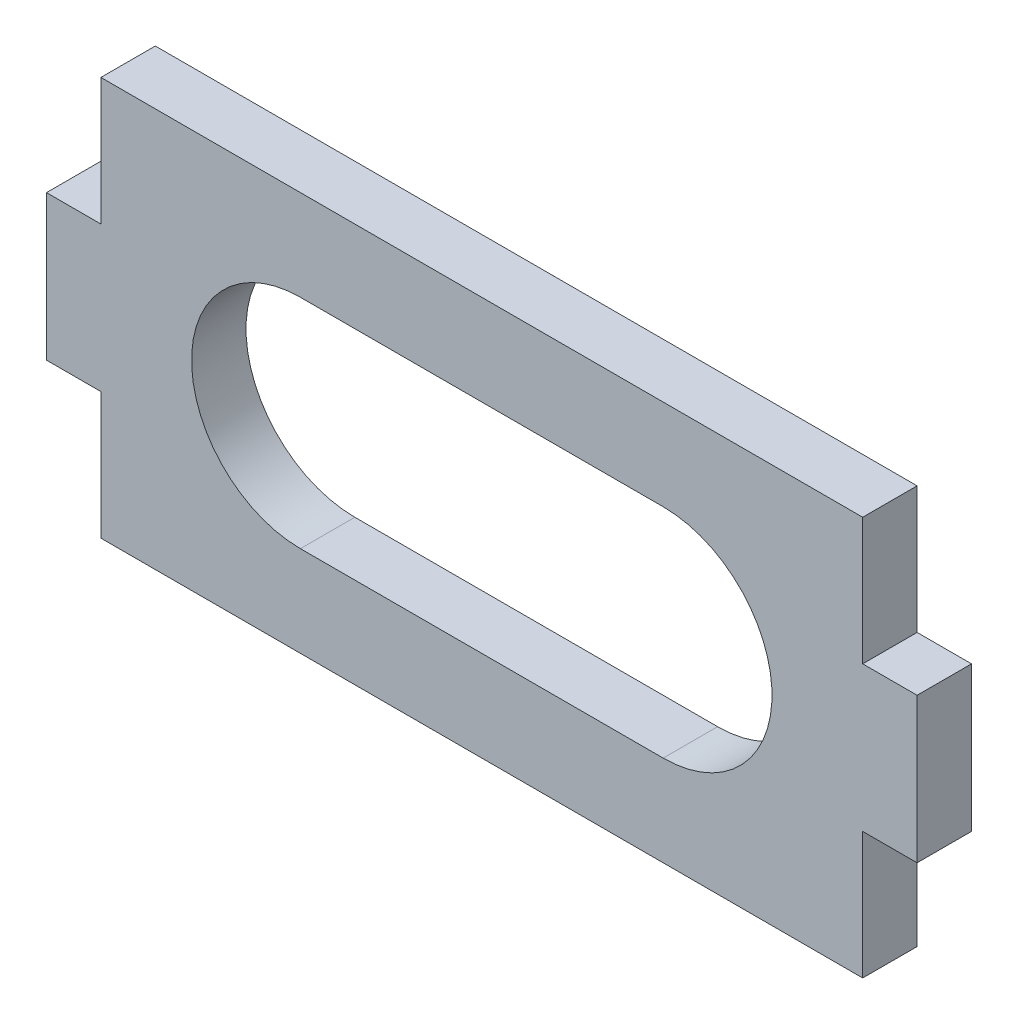
SolidWorks part; units mm, degrees
ref_plane "Płaszczyzna przednia" through (0, 0, 0) normal (0, 0, 1) x (1, 0, 0)
ref_plane "Płaszczyzna górna" through (0, 0, 0) normal (0, 1, 0) x (1, 0, 0)
ref_plane "Płaszczyzna prawa" through (0, 0, 0) normal (1, 0, 0) x (0, 0, -1)
sketch "Szkic1" plane through (0, 0, 0) normal (0, 0, 1) x (1, 0, 0)
  line L0 (0, 0) -> (0, 57.4837) construction
  line L1 (-21, 11) -> (21, 11)
  line L2 (-21, 11) -> (-21, 4)
  line L3 (-21, -11) -> (21, -11)
  line L4 (21, 11) -> (21, 4)
  line L5 (-21, 11) -> (21, -11) construction
  line L6 (-21, -11) -> (21, 11) construction
  line L7 (21, -4) -> (24, -4)
  line L8 (-21, 4) -> (-24, 4)
  line L9 (21, -4) -> (21, -11)
  line L10 (-21, -4) -> (-24, -4)
  line L11 (-24, 4) -> (-24, -4)
  line L12 (24, 4) -> (24, -4)
  line L13 (21, 4) -> (24, 4)
  line L14 (-21, 4) -> (-21, -4) construction
  line L15 (-21, -4) -> (-21, -11)
  line L16 (21, 4) -> (21, -4) construction
  line L17 (-10, 0) -> (10, 0) construction
  line L18 (-10, 6) -> (10, 6)
  line L19 (-10, -6) -> (10, -6)
  line L20 (-24, 0) -> (-10, 0) construction
  arc A0 (-10, 6) -> (-10, -6) centre (-10, 0) ccw
  arc A1 (10, -6) -> (10, 6) centre (10, 0) ccw
  point P0 (0, 0)
  point P18 (0, 0)
  dimension "D1" = 48
  dimension "D2" = 22
  dimension "D3" = 8
  dimension "D4" = 3
  dimension "D5" = 12
  dimension "D6" = 20
extrude "Dodanie-wyciągnięcie1" add sketch "Szkic1" along normal blind 3
